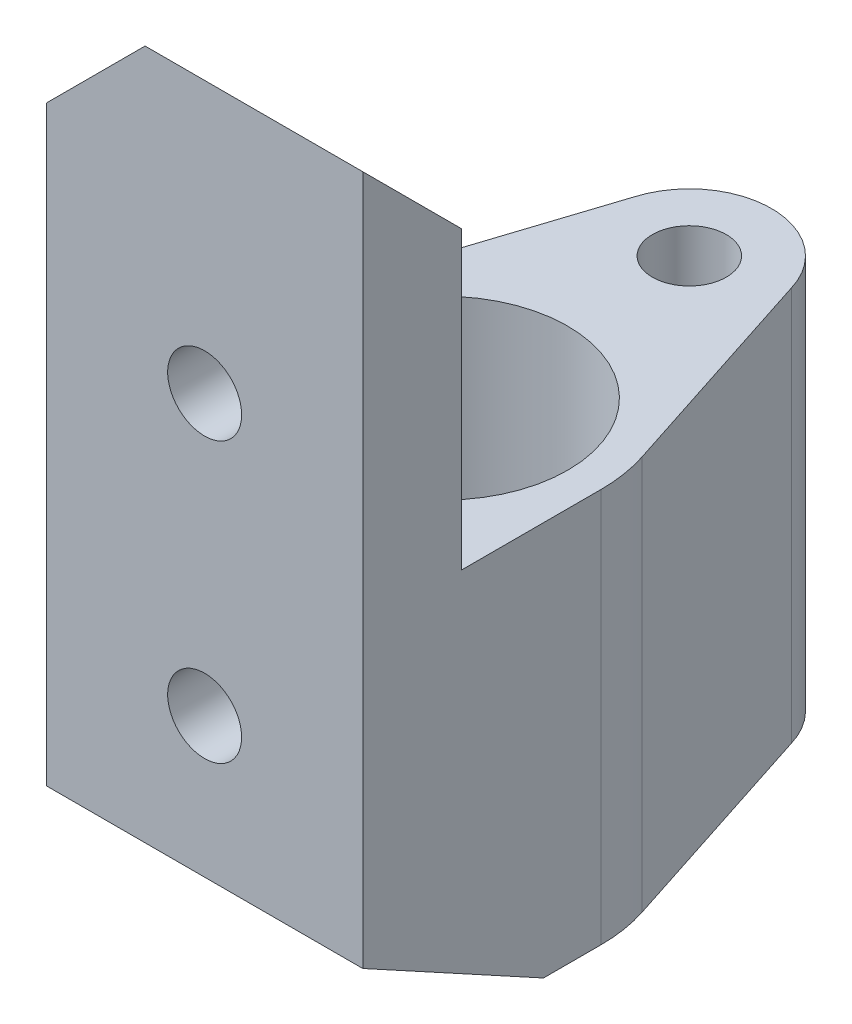
SolidWorks part; units mm, degrees
ref_plane "Front Plane" through (0, 0, 0) normal (0, 0, 1) x (1, 0, 0)
ref_plane "Top Plane" through (0, 0, 0) normal (0, 1, 0) x (1, 0, 0)
ref_plane "Right Plane" through (0, 0, 0) normal (1, 0, 0) x (0, 0, -1)
sketch "Sketch1" plane through (0, 0, 0) normal (0, 1, 0) x (1, 0, 0)
  line L0 (0, 15) -> (0, 0) construction
  line L1 (-9.625, -8.5) -> (9.625, -8.5)
  line L2 (-9.625, 0) -> (9.625, 0) construction
  line L3 (-9.625, -8.5) -> (-9.625, 0)
  line L4 (-9.625, 0) -> (-4.7967, 16.4112) construction
  line L5 (9.625, 0) -> (4.7967, 16.4112) construction
  line L6 (9.625, -8.5) -> (9.625, 0)
  line L7 (-4.7967, 16.4112) -> (-9.1557, 2.9689)
  line L8 (4.7967, 16.4112) -> (9.1557, 2.9689)
  circle A0 centre (0, 0) radius 7.6
  circle A1 centre (0, 15) radius 2.25
  circle A2 centre (0, 15) radius 5 construction
  circle A3 centre (0, 0) radius 9.625 construction
  arc A4 (-4.7967, 16.4112) -> (4.7967, 16.4112) centre (0, 15) cw
  arc A5 (-9.1557, 2.9689) -> (-9.625, 0) centre (0, 0) ccw
  arc A6 (9.1557, 2.9689) -> (9.625, 0) centre (0, 0) cw
  point P10 (0, -8.5)
  point P13 (0, 0)
  dimension "D2" = 15.2
  dimension "D3" = 4.5
  dimension "D4" = 10
  dimension "D5" = 19.25
  dimension "D1" = 15
  dimension "D6" = 8.5
extrude "Boss-Extrude1" add sketch "Sketch1" along normal blind 24
sketch "Sketch3" plane through (-9.625, 0, 0) normal (-1, 0, 0) x (0, 0, 1)
  line L0 (8.5, 0) -> (14.5, 0)
  line L1 (14.5, 48) -> (14.5, 0)
  line L4 (14.5, 48) -> (8.5, 48)
  line L5 (8.5, 48) -> (8.5, 24)
  line L6 (8.5, 0) -> (8.5, 24)
  dimension "D1" = 48
  dimension "D2" = 6
extrude "Boss-Extrude2" add sketch "Sketch3" against normal blind 19.25
sketch "Sketch4" plane through (9.625, 0, 0) normal (1, 0, 0) x (0, 0, -1)
  line L0 (-14.5, 0) -> (-14.5, 6)
  line L1 (-14.5, 0) -> (-14.5, 48) construction
  line L2 (-14.5, 6) -> (-3.5, 0)
  line L3 (-14.5, 0) -> (0, 0) construction
  line L4 (-3.5, 0) -> (-14.5, 0)
  dimension "D1" = 6
  dimension "D2" = 11
extrude "Cut-Extrude1" cut sketch "Sketch4" against normal through all
chamfer "Chamfer1" distance 6 distance2 6 1 edges at (-9.625, 48, 11.5)
sketch "Sketch6" plane through (0, 0, 14.5) normal (0, 0, 1) x (1, 0, 0)
  circle A0 centre (0, 14.5043) radius 2.25
  circle A1 centre (0, 31.5) radius 2.25
  dimension "D1" = 4.5
  dimension "D2" = 4.5
extrude "Cut-Extrude3" cut sketch "Sketch6" against normal blind 16
chamfer "Chamfer2" distance 6 distance2 6 1 edges at (3, 48, 8.5)
